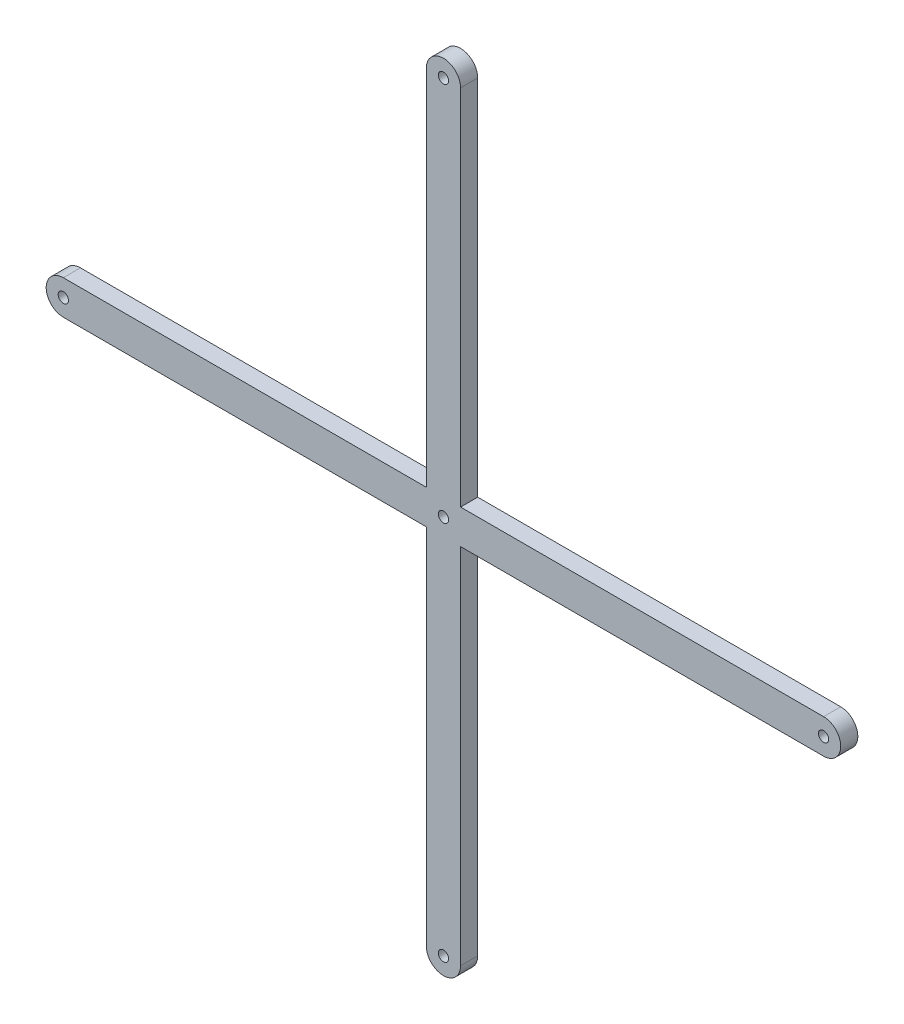
SolidWorks part; units mm, degrees
ref_plane "Front Plane" through (0, 0, 0) normal (0, 0, 1) x (1, 0, 0)
ref_plane "Top Plane" through (0, 0, 0) normal (0, 1, 0) x (1, 0, 0)
ref_plane "Right Plane" through (0, 0, 0) normal (1, 0, 0) x (0, 0, -1)
sketch "Sketch1" plane through (0, 0, 0) normal (0, 0, 1) x (1, 0, 0)
  line L0 (111, 0) -> (-111, 0) construction
  line L1 (5, -5) -> (5, -111)
  line L2 (-5, -5) -> (-5, -111)
  line L3 (0, 111) -> (0, -111) construction
  line L5 (-5, 5) -> (-111, 5)
  line L6 (-5, -5) -> (-111, -5)
  line L7 (5, 5) -> (5, 111)
  line L8 (-5, 5) -> (-5, 111)
  line L9 (5, -5) -> (111, -5)
  line L10 (5, 5) -> (111, 5)
  arc A1 (-5, -111) -> (5, -111) centre (0, -111) ccw
  circle A2 centre (0, 0) radius 1.5
  circle A3 centre (0, -111) radius 1.5
  arc A4 (-111, 5) -> (-111, -5) centre (-111, 0) ccw
  arc A5 (5, 111) -> (-5, 111) centre (0, 111) ccw
  arc A6 (111, -5) -> (111, 5) centre (111, 0) ccw
  circle A7 centre (-111, 0) radius 1.5
  circle A8 centre (0, 111) radius 1.5
  circle A9 centre (111, 0) radius 1.5
  point P0 (0, 0)
  point P3 (0, -55.5)
  point P34 (0, 0)
  point P37 (0, 0)
  dimension "D2" = 4
  dimension "D3" = 3
  dimension "D4" = 3
  dimension "D5" = 5
  dimension "D6" = 4
extrude "Boss-Extrude1" add sketch "Sketch1" along normal blind 5
